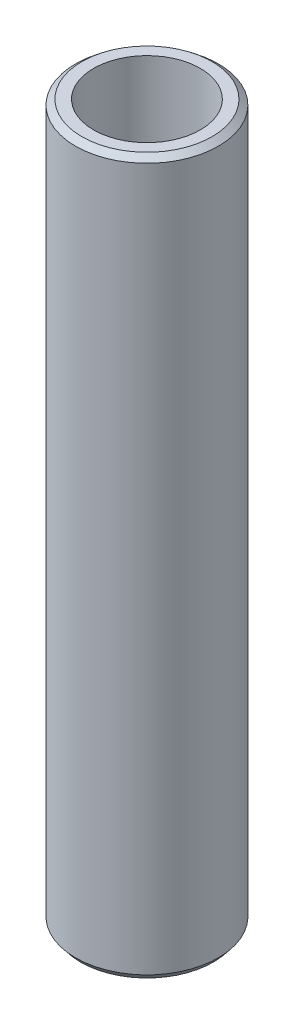
SolidWorks part; units mm, degrees
ref_plane "Front Plane" through (0, 0, 0) normal (0, 0, 1) x (1, 0, 0)
ref_plane "Top Plane" through (0, 0, 0) normal (0, 1, 0) x (1, 0, 0)
ref_plane "Right Plane" through (0, 0, 0) normal (1, 0, 0) x (0, 0, -1)
sketch "Sketch1" plane through (0, 0, 0) normal (0, 1, 0) x (1, 0, 0)
  circle A0 centre (0, 0) radius 55
  dimension "SHAFT_OD" = 110
extrude "Boss-Extrude1" add sketch "Sketch1" along normal blind 550.1693
sketch "Sketch2" plane through (0, 0, 0) normal (0, 1, 0) x (1, 0, 0)
  circle A0 centre (0, 0) radius 41.0896
  dimension "BORE_D" = 82.1793
extrude "Cut-Extrude1" cut sketch "Sketch2" along normal through all
chamfer "Chamfer1" distance 3.9139 angle 51.157 2 edges at (0, 550.1693, 55) (0, 0, 55) first distance on face at (0, 550.1693, 55) first distance on face at (0, 0, 41.0896)
